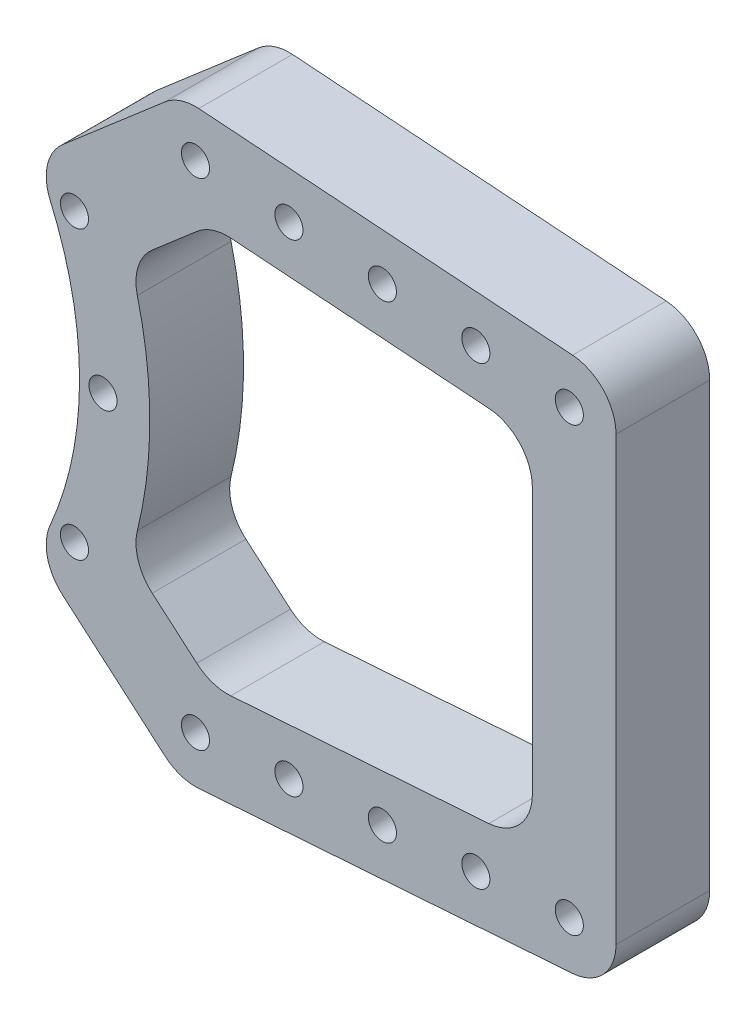
SolidWorks part; units mm, degrees
ref_plane "前视基准面" through (0, 0, 0) normal (0, 0, 1) x (1, 0, 0)
ref_plane "上视基准面" through (0, 0, 0) normal (0, 1, 0) x (1, 0, 0)
ref_plane "右视基准面" through (0, 0, 0) normal (1, 0, 0) x (0, 0, -1)
other "Configuration Table"
sketch "草图3" plane through (0, 0, 0) normal (0, 0, 1) x (1, 0, 0)
  line L0 (36.9552, -15.3073) -> (49.8729, -26.4376)
  line L1 (49.8729, -26.4376) -> (99.7459, -22.8753)
  line L2 (99.7459, -22.8753) -> (109.9739, -12.4372)
  line L3 (36.9552, 15.3073) -> (49.8729, 26.4376)
  line L4 (49.8729, 26.4376) -> (99.7459, 22.8753)
  line L5 (99.7459, 22.8753) -> (109.9739, 12.4372)
  line L6 (32.4388, -18.0159) -> (48.1718, -31.5719)
  line L7 (48.1718, -31.5719) -> (101.9915, -27.7276)
  line L8 (101.9915, -27.7276) -> (114.1851, -15.2836)
  line L9 (40.2189, -11.5195) -> (51.5741, -21.3034)
  line L10 (51.5741, -21.3034) -> (97.5003, -18.023)
  line L11 (97.5003, -18.023) -> (106.4026, -8.9378)
  line L12 (40.2189, 11.5195) -> (51.5741, 21.3034)
  line L13 (51.5741, 21.3034) -> (97.5003, 18.023)
  line L14 (97.5003, 18.023) -> (106.4026, 8.9378)
  line L15 (32.0167, 17.6522) -> (48.1718, 31.5719)
  line L16 (48.1718, 31.5719) -> (101.9915, 27.7276)
  line L17 (101.9915, 27.7276) -> (114.1732, 15.2957)
  line L18 (33.6914, -19.0952) -> (48.1718, -31.5719) construction
  line L19 (33.6914, 19.0952) -> (48.1718, 31.5719) construction
  line L20 (101.9915, -27.7276) -> (113.5452, -15.9366) construction
  line L21 (101.9915, 27.7276) -> (113.5452, 15.9366) construction
  line L22 (112.379, 17.1268) -> (115.1724, 14.276)
  circle A0 centre (140, 0) radius 32.5
  circle A1 centre (0, 0) radius 40
  circle A2 centre (140, 0) radius 35
  circle A4 centre (0, 0) radius 45
  circle A5 centre (0, 0) radius 37.5
  circle A6 centre (140, 0) radius 30
  dimension "D5" = 75
  dimension "D6" = 60
  dimension "D1" = 5
  dimension "D2" = 5
  dimension "D3" = 5
  dimension "D4" = 5
extrude "凸台-拉伸1" add sketch "草图3" along normal blind 15 contours A4 L6 L7 L8 A2 L2 L1 L0 | L2 A2 L8 A0 | A6 L22 L17 A0 L8 | L5 A2 L2 A0 | L17 A2 L5 A0 | A4 L3 L4 L5 A2 L17 L16 L15 | A4 L12 L13 L14 A2 L5 L4 L3 | A4 L0 L1 L2 A2 L11 L10 L9 | A4 L3 A1 L0 | L6 A4 L0 A1 | A5 L6 A1 L15 | L3 A4 L15 A1 region at (41.3867, 0, 0) region at (35.5259, -17.4826, 0) region at (37.8147, -19.3316, 0) region at (74.8342, -20.827, 0) region at (74.7979, -25.8688, 0) region at (37.8147, 19.3316, 0) region at (74.7979, 25.8688, 0) region at (74.8342, 20.827, 0) region at (107.1526, 0, 0) region at (110.1942, -15.7548, 0) region at (107.849, 0, 0) region at (110.1942, 15.7548, 0)
fillet "圆角1" radius 5 1 edges at (101.9915, 27.7276, 7.5) type face fillet first side face at (75.0816, 29.6498, 7.5) second side face at (108.0883, 21.5056, 7.5)
fillet "圆角2" radius 5 1 edges at (114.1851, 15.2836, 7.5) type face fillet first side face at (108.7511, 20.8292, 7.5) second side face at (112.0925, 0, 7.5)
fillet "圆角3" radius 5 1 edges at (114.1851, -15.2836, 7.5) type face fillet first side face at (111.7305, -1.5791, 7.5) second side face at (108.0883, -21.5056, 7.5)
fillet "圆角4" radius 5 1 edges at (101.9915, -27.7276, 7.5) type face fillet first side face at (75.0816, -29.6498, 7.5) second side face at (106.8234, -22.7964, 7.5)
fillet "圆角5" radius 5 1 edges at (48.1718, -31.5719, 7.5) type face fillet first side face at (40.4577, -24.9252, 7.5) second side face at (74.1369, -29.7172, 7.5)
fillet "圆角6" radius 5 1 edges at (48.1718, 31.5719, 7.5) type face fillet first side face at (40.4577, 24.9252, 7.5) second side face at (74.1369, 29.7172, 7.5)
fillet "圆角7" radius 5 1 edges at (32.7436, -18.2785, 7.5) type face fillet first side face at (35.1218, 0, 7.5) second side face at (39.6764, -24.252, 7.5)
fillet "圆角8" radius 5 1 edges at (32.7436, 18.2785, 7.5) type face fillet first side face at (39.6764, 24.252, 7.5) second side face at (35.5042, 1.7252, 7.5)
fillet "圆角9" radius 5 1 edges at (97.5003, -18.023, 7.5) type face fillet first side face at (74.5372, -19.6632, 7.5) second side face at (101.8563, -13.5775, 7.5)
fillet "圆角10" radius 5 1 edges at (106.2123, -9.132, 7.5) type face fillet first side face at (102.5192, -12.901, 7.5) second side face at (105.6062, 0, 7.5)
fillet "圆角11" radius 5 1 edges at (106.2123, 9.132, 7.5) type face fillet first side face at (105.4736, 1.2632, 7.5) second side face at (101.8563, 13.5775, 7.5)
fillet "圆角12" radius 5 1 edges at (97.5003, 18.023, 7.5) type face fillet first side face at (74.5372, 19.6632, 7.5) second side face at (100.8988, 14.5546, 7.5)
fillet "圆角13" radius 5 1 edges at (51.5741, -21.3034, 7.5) type face fillet first side face at (47.2066, -17.5403, 7.5) second side face at (73.5925, -19.7307, 7.5)
fillet "圆角14" radius 5 1 edges at (42.8391, -13.7771, 7.5) type face fillet first side face at (46.4253, -16.8671, 7.5) second side face at (43.9196, 0, 7.5)
fillet "圆角15" radius 5 1 edges at (42.8391, 13.7771, 7.5) type face fillet first side face at (44.1142, 1.4849, 7.5) second side face at (47.2066, 17.5403, 7.5)
fillet "圆角16" radius 5 1 edges at (51.5741, 21.3034, 7.5) type face fillet first side face at (48.4155, 18.5819, 7.5) second side face at (73.5925, 19.7307, 7.5)
sketch "草图5" plane through (0, 0, 0) normal (0, 0, -1) x (-1, 0, 0)
  circle A0 centre (-36.9552, 15.3073) radius 1.5
  circle A1 centre (-40, 0) radius 1.5
  circle A2 centre (-36.9552, -15.3073) radius 1.5
  circle A3 centre (-49.8729, -26.4376) radius 1.5
  circle A4 centre (-49.8729, 26.4376) radius 1.5
  circle A5 centre (-99.7459, 22.8753) radius 1.5
  circle A6 centre (-99.7459, -22.8753) radius 1.5
  circle A7 centre (-109.9739, 12.4372) radius 1.5
  circle A8 centre (-107.5, 0) radius 1.5
  circle A9 centre (-109.9739, -12.4372) radius 1.5
  circle A10 centre (-59.8475, 25.7252) radius 1.5
  circle A11 centre (-69.8221, 25.0127) radius 1.5
  circle A12 centre (-79.7967, 24.3002) radius 1.5
  circle A13 centre (-89.7713, 23.5878) radius 1.5
  circle A14 centre (-89.7713, -23.5878) radius 1.5
  circle A15 centre (-79.7967, -24.3002) radius 1.5
  circle A16 centre (-69.8221, -25.0127) radius 1.5
  circle A17 centre (-59.8475, -25.7252) radius 1.5
extrude "切除-拉伸1" cut sketch "草图5" against normal blind 15
sketch "草图6" plane through (0, 0, 15) normal (0, 0, 1) x (1, 0, 0)
  line L0 (100.1021, 27.8626) -> (100.1021, -27.8626)
  line L1 (100.1021, 27.8626) -> (115.1226, 26.777)
  line L2 (4.9746, 34.6447) -> (140, 25) construction
  line L3 (115.1226, 26.777) -> (132.6157, -67.8734)
  line L4 (132.6157, -67.8734) -> (100.1021, -27.8626)
  line L5 (99.7459, 22.8753) -> (89.7713, 23.5878)
  line L6 (99.7459, -22.8753) -> (89.7713, -23.5878)
  line L7 (94.7586, 23.2315) -> (94.7586, -23.2315)
  line L8 (94.7586, 23.2315) -> (94.7586, 28.2443)
  line L9 (50.2292, 31.4249) -> (100.1021, 27.8626) construction
  line L10 (94.7586, 28.2443) -> (100.1021, 27.8626)
  line L11 (94.7586, -23.2315) -> (94.7586, -28.2443)
  line L12 (50.2292, -31.4249) -> (100.1021, -27.8626) construction
  line L13 (94.7586, -28.2443) -> (100.1021, -27.8626)
  circle M8 centre (109.9739, -12.4372) radius 1.5
  circle M13 centre (107.5, 0) radius 1.5
  circle M14 centre (109.9739, 12.4372) radius 1.5
  circle M15 centre (99.7459, -22.8753) radius 1.5
  circle M16 centre (99.7459, 22.8753) radius 1.5
  line M24 (53.6315, 21.1564) -> (95.6109, 18.1579)
  arc M25 (95.6109, 18.1579) -> (98.826, 16.67) centre (95.2547, 13.1706) cw
  line M26 (98.826, 16.67) -> (104.2974, 11.0863)
  arc M27 (104.2974, 11.0863) -> (105.6353, 6.6385) centre (100.7261, 7.5869) cw
  arc M28 (105.6353, 6.6385) -> (105.6353, -6.6385) centre (140, 0) ccw
  arc M29 (105.6353, -6.6385) -> (104.2974, -11.0863) centre (100.7261, -7.5869) cw
  line M30 (104.2974, -11.0863) -> (98.826, -16.67)
  arc M31 (98.826, -16.67) -> (95.6109, -18.1579) centre (95.2547, -13.1706) cw
  line M32 (95.6109, -18.1579) -> (53.6315, -21.1564)
  line M45 (50.2292, -31.4249) -> (100.1021, -27.8626)
  arc M46 (100.1021, -27.8626) -> (103.3172, -26.3747) centre (99.7459, -22.8753) ccw
  line M47 (103.3172, -26.3747) -> (111.6554, -17.8652)
  arc M48 (111.6554, -17.8652) -> (112.6435, -12.3136) centre (108.0841, -14.3658) ccw
  arc M49 (112.6435, -12.3136) -> (112.6435, 12.3136) centre (140, 0) cw
  arc M50 (112.6435, 12.3136) -> (111.6554, 17.8652) centre (108.0841, 14.3658) ccw
  line M51 (111.6554, 17.8652) -> (103.3172, 26.3747)
  arc M52 (103.3172, 26.3747) -> (100.1021, 27.8626) centre (99.7459, 22.8753) ccw
  line M53 (100.1021, 27.8626) -> (50.2292, 31.4249)
extrude "切除-拉伸5" cut sketch "草图6" against normal blind 15 contours L0 M52 M16 M26 M27 M28 M29 M30 M15 M46 M47 M48 M49 M50 M51 M13 M14 M8 | L7 L6 L0 M32 M15 M30 M31 | L6 L11 L0 M45 M15 | L5 L7 L0 M24 M25 M26 M16 | L8 L5 L0 M16 M53 region at (101.6055, 26.8937, 15) region at (97.2597, 25.7269, 15) region at (97.4802, 19.9531, 15) region at (97.2597, -25.7269, 15) region at (97.4802, -19.9531, 15)
sketch "草图7" plane through (0, 0, 15) normal (0, 0, 1) x (1, 0, 0)
  line L0 (94.7586, 18.2188) -> (85.8268, 18.8568)
  line L1 (94.7586, 28.2443) -> (85.8268, 28.2443)
  line L2 (94.7586, 28.2443) -> (94.7586, -28.2443)
  line L3 (94.7586, -28.2443) -> (85.8268, -28.2443)
  line L4 (85.8268, 28.2443) -> (85.8268, -28.2443)
  line L5 (53.6315, 21.1564) -> (94.7586, 18.2188) construction
  line L6 (94.7586, -18.2188) -> (85.8268, -18.8568)
  line L7 (53.6315, -21.1564) -> (94.7586, -18.2188) construction
  line M3 (94.7586, -18.2188) -> (53.6315, -21.1564)
  line M11 (53.6315, 21.1564) -> (94.7586, 18.2188)
extrude "凸台-拉伸2" add sketch "草图7" against normal blind 15 contours L4 L2 M11 M3 region at (90.2671, 0, 15)
fillet "圆角17" radius 5 1 edges at (94.7586, 28.2443, 7.5) type face fillet first side face at (72.4939, 29.8346, 7.5) second side face at (94.7586, 0, 7.5)
fillet "圆角18" radius 5 1 edges at (94.7586, -28.2443, 7.5) type face fillet first side face at (94.7586, -2.3278, 7.5) second side face at (72.4939, -29.8346, 7.5)
fillet "圆角19" radius 5 1 edges at (85.8268, 18.8568, 7.5) type face fillet first side face at (85.8268, 0, 7.5) second side face at (69.7291, 20.0066, 7.5)
fillet "圆角20" radius 5 1 edges at (85.8268, -18.8568, 7.5) type face fillet first side face at (85.8268, -2.3278, 7.5) second side face at (69.7291, -20.0066, 7.5)
sketch "草图8" plane through (0, 0, 0) normal (0, 0, -1) x (-1, 0, 0)
  line L1 (-115.5106, 32.3706) -> (-18.9905, 32.3706)
  line L2 (-115.5106, 32.3706) -> (-115.5106, -39.9455)
  line L3 (-115.5106, -39.9455) -> (-18.9905, -39.9455)
  line L4 (-18.9905, 32.3706) -> (-18.9905, -39.9455)
  line L5 (-115.5106, 32.3706) -> (-18.9905, -39.9455) construction
  line L6 (-115.5106, -39.9455) -> (-18.9905, 32.3706) construction
  point P0 (-67.2506, -3.7874)
  point P5 (-18.9905, -39.9455)
extrude "切除-拉伸6" cut sketch "草图8" against normal blind 5
